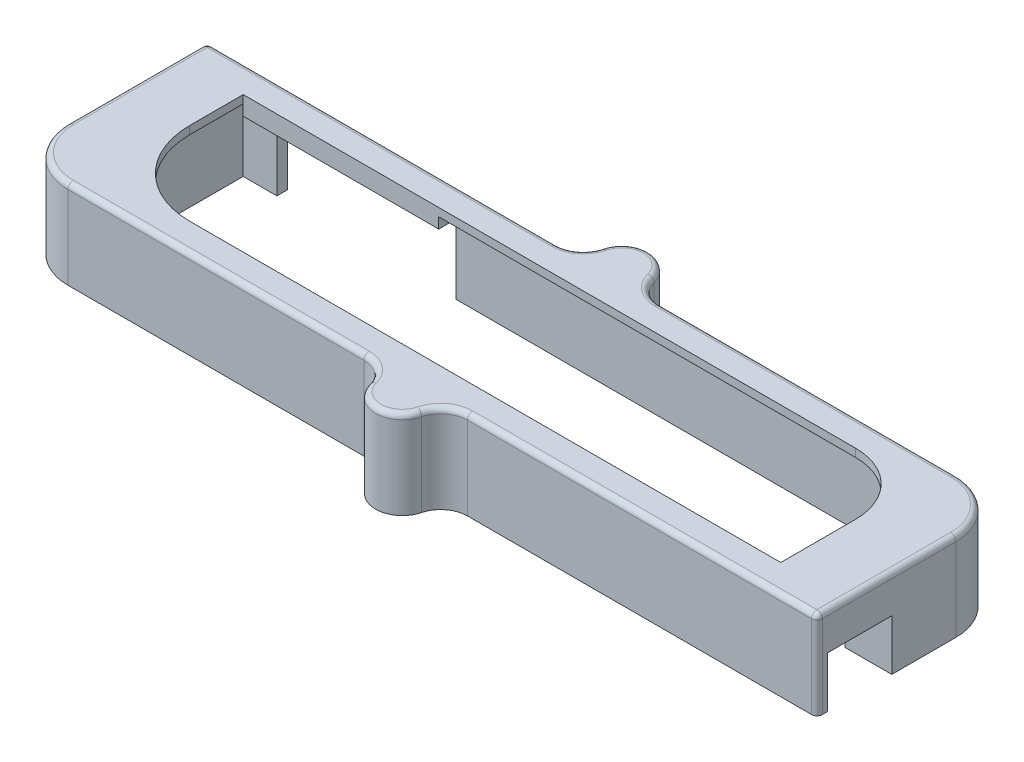
SolidWorks part; units mm, degrees
ref_plane "Front Plane" through (0, 0, 0) normal (0, 0, 1) x (1, 0, 0)
ref_plane "Top Plane" through (0, 0, 0) normal (0, 1, 0) x (1, 0, 0)
ref_plane "Right Plane" through (0, 0, 0) normal (1, 0, 0) x (0, 0, -1)
sketch "Sketch1" plane through (0, 0, 0) normal (0, 1, 0) x (1, 0, 0)
  line L7 (0, 0) -> (-110.5, 0)
  line L8 (-126, 15.5) -> (-126, 25.5)
  line L9 (-126, 25.5) -> (-11.5, 25.5)
  line L10 (0, 14) -> (0, 0)
  line L11 (-138, 30.75) -> (12, 30.75)
  line L12 (12, -5.25) -> (-138, -5.25)
  line L13 (0, -5.25) -> (-110.5, -5.25) construction
  line L14 (-126, 30.75) -> (-11.5, 30.75) construction
  line L15 (-138, 30.75) -> (-138, -5.25)
  line L16 (12, 30.75) -> (12, -5.25)
  arc A1 (-110.5, 0) -> (-126, 15.5) centre (-110.5, 15.5) cw
  arc A2 (-11.5, 25.5) -> (0, 14) centre (-11.5, 14) cw
  dimension "D1" = 25.5
  dimension "D2" = 126
  dimension "D3" = 10
  dimension "D4" = 14
  dimension "D6" = 12
  dimension "D7" = 12
  dimension "D5" = 5.25
extrude "Boss-Extrude1" add sketch "Sketch1" along normal blind 1.5
sketch "Sketch2" plane through (0, 0, 0) normal (0, -1, 0) x (1, 0, 0)
  line L0 (12, 5.25) -> (12, -30.75) construction
  line L1 (-138, -30.75) -> (-138, 5.25) construction
  line L2 (12, -30.75) -> (-138, -30.75) construction
  line L3 (-138, 5.25) -> (12, 5.25) construction
  line L4 (12, 5.25) -> (12, -30.75)
  line L5 (-138, -30.75) -> (-138, 5.25)
  line L6 (12, -30.75) -> (-138, -30.75)
  line L7 (-138, 5.25) -> (12, 5.25)
  line L9 (3.25, -28.75) -> (-129.25, -28.75)
  line L11 (-129.25, 3.25) -> (3.25, 3.25)
  line L12 (10, 3.25) -> (10, -28.75) construction
  line L13 (-136, -28.75) -> (-136, 3.25) construction
  line L22 (-129.25, 3.25) -> (-129.25, -28.75)
  line L23 (-136, 3.25) -> (10, 3.25) construction
  line L24 (10, -28.75) -> (-136, -28.75) construction
  line L25 (3.25, 3.25) -> (3.25, -28.75)
  line L26 (0, 0) -> (0, -14) construction
  line L27 (-126, -25.5) -> (-126, -15.5) construction
  point P14 (-126, -20.5)
  dimension "D2" = 3.25
  dimension "D3" = 3.25
  dimension "D1" = 2
extrude "Boss-Extrude2" add sketch "Sketch2" along normal blind 15
sketch "Sketch3" plane through (12, 0, 0) normal (-1, 0, 0) x (0, 0, 1)
  line L0 (5.25, -15) -> (-30.75, -15) construction
  line L1 (-8.75, -15) -> (3.25, -15)
  line L2 (-8.75, -15) -> (-8.75, -5.5)
  line L3 (-8.75, -5.5) -> (3.25, -5.5)
  line L4 (3.25, -15) -> (3.25, -5.5)
  line L5 (3.25, -15) -> (3.25, 0) construction
  line L6 (3.25, 0) -> (-28.75, 0) construction
  dimension "D1" = 12
  dimension "D2" = 5.5
extrude "Cut-Extrude1" cut sketch "Sketch3" against normal up to surface (-141.25 mm away) up to face at (-129.25, -7.5, -12.75)
sketch "Sketch4" plane through (0, 0, -30.75) normal (0, 0, 1) x (1, 0, 0)
  line L0 (-129.25, -15) -> (-129.25, 0) construction
  line L7 (12, -15) -> (-138, -15) construction
  line L12 (-122.95, -2) -> (-89.45, -2)
  line L13 (-122.95, -2) -> (-122.95, -15)
  line L14 (-122.95, -15) -> (-89.45, -15)
  line L15 (-89.45, -2) -> (-89.45, -15)
  line L19 (3.25, 0) -> (-129.25, 0) construction
  dimension "D1" = 2
  dimension "D2" = 33.5
  dimension "D3" = 6.3
extrude "Cut-Extrude2" cut sketch "Sketch4" against normal up to surface (-34 mm away) up to face at (-38, -6.8333, 3.25)
sketch "Sketch9" plane through (0, 1.5, 0) normal (0, 1, 0) x (1, 0, 0)
  line L0 (-68, 33.25) -> (-68, 30.75)
  line L1 (12, 30.75) -> (-138, 30.75) construction
  line L2 (-68, 30.75) -> (-58, 30.75)
  line L3 (-58, 30.75) -> (-58, 33.25)
  line L4 (-58, -7.75) -> (-58, -5.25)
  line L5 (-138, -5.25) -> (12, -5.25) construction
  line L6 (-58, -5.25) -> (-68, -5.25)
  line L7 (-68, -5.25) -> (-68, -7.75)
  line L8 (-138, 12.75) -> (-63, 12.75) construction
  line L9 (-138, 30.75) -> (-138, -5.25) construction
  line L10 (-63, 12.75) -> (12, 12.75) construction
  line L11 (12, -5.25) -> (12, 30.75) construction
  arc A3 (-68, 33.25) -> (-58, 33.25) centre (-63, 33.25) cw
  arc A4 (-58, -7.75) -> (-68, -7.75) centre (-63, -7.75) cw
  dimension "D1" = 2.5
  dimension "D2" = 10
extrude "Boss-Extrude4" add sketch "Sketch9" against normal up to surface (16.5 mm away) up to face at (-24.7333, -15, -22.75)
fillet "Fillet1" radius 10 2 edges at (12, -6.75, -30.75) (-138, -6.75, 5.25)
sketch "Sketch5" plane through (0, -15, 0) normal (0, 1, 0) x (1, 0, 0)
  line L0 (-126, 25.5) -> (-126, 15.5) construction
  line L1 (0, 0) -> (0, 14) construction
  line L2 (-11.5, 25.5) -> (-126, 25.5) construction
  line L3 (-110.5, 0) -> (0, 0) construction
  circle A0 centre (7.5, 21.5) radius 1.375
  circle A1 centre (7.5, 4) radius 1.375
  circle A2 centre (-133.5, 4) radius 1.375
  circle A3 centre (-133.5, 21.5) radius 1.375
  circle A4 centre (-63, -7.75) radius 1.375
  circle A5 centre (-63, 33.25) radius 1.375
  dimension "D1" = 2.75
  dimension "D2" = 7.5
  dimension "D3" = 7.5
  dimension "D4" = 4
  dimension "D5" = 4
extrude "Cut-Extrude3" cut sketch "Sketch5" along normal blind 7.5
sketch "Sketch8" plane through (0, 0, 0) normal (0, -1, 0) x (1, 0, 0)
  line L0 (-129.25, -28.75) -> (3.25, -28.75) construction
  line L1 (-126, -25.5) -> (-89.45, -25.5)
  line L2 (-126, -25.5) -> (-126, -28.75)
  line L3 (-126, -28.75) -> (-89.45, -28.75)
  line L4 (-89.45, -25.5) -> (-89.45, -28.75)
extrude "Boss-Extrude3" add sketch "Sketch8" along normal blind 2
fillet "Fillet2" radius 5 4 edges at (-58, -6.75, 5.25) (-68, -6.75, 5.25) (-58, -6.75, -30.75) (-68, -6.75, -30.75)
fillet "Fillet3" radius 1 14 edges at (-100.3412, 1.5, 5.25) (-56.3794, 1.5, 6.2972) (-63, 1.5, 12.75) (-69.6206, 1.5, 6.2972) (-135.0711, 1.5, 2.3211) (12, 1.5, -7.75) (9.0711, 1.5, -27.8211) (-25.6588, 1.5, -30.75) (-56.3794, 1.5, -31.7972) (-63, 1.5, -38.25) (-69.6206, 1.5, -31.7972) (-138, 1.5, -17.75) (12, -6.75, 5.25) (-138, -6.75, -30.75)
chamfer "Chamfer1" distance 1 angle 45 5 edges at (-63, -15, 9.125) (-133.5, -15, -2.625) (-133.5, -15, -20.125) (-63, -15, -31.875) (7.5, -15, -20.125)
sketch "Sketch10" plane through (0, 0, 0) normal (0, -1, 0) x (1, 0, 0)
  line L0 (3.25, -28.75) -> (3.25, 3.25) construction
  line L1 (3.25, 0) -> (-110.5, 0)
  line L2 (3.25, 0) -> (3.25, 3.25)
  line L3 (3.25, 3.25) -> (-110.5, 3.25)
  line L4 (-110.5, 0) -> (-110.5, 3.25)
  line L5 (3.25, 3.25) -> (-129.25, 3.25) construction
  line L6 (-110.5, 0) -> (0, 0) construction
extrude "Cut-Extrude4" cut sketch "Sketch10" against normal blind 0.25
equation "\"T\"= 0.25'Print Tolerance"
equation "\"D1@Sketch1\"=25+0.25+\"T\""
equation "\"D3@Sketch1\"=9.75+\"T\""
equation "\"D5@Sketch1\"=5.00+\"T\""
equation "\"D2@Sketch2\"=3+\"T\""
equation "\"D3@Sketch2\"=\"D2@Sketch2\""
equation "\"D1@Sketch3\"=11.75+\"T\""
